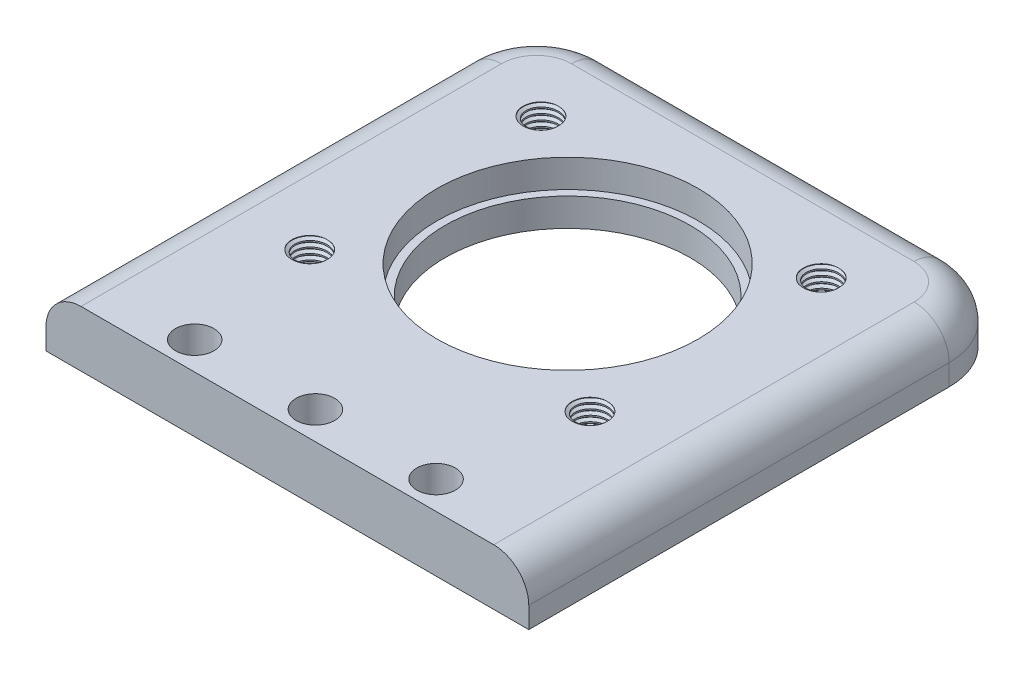
SolidWorks part; units mm, degrees
ref_plane "Front Plane" through (0, 0, 0) normal (0, 0, 1) x (1, 0, 0)
ref_plane "Top Plane" through (0, 0, 0) normal (0, 1, 0) x (1, 0, 0)
ref_plane "Right Plane" through (0, 0, 0) normal (1, 0, 0) x (0, 0, -1)
sketch "Sketch1" plane through (0, 0, 0) normal (0, 1, 0) x (1, 0, 0)
  line L1 (0, 0) -> (68.9, 0)
  line L2 (0, 0) -> (0, 70)
  line L3 (0, 70) -> (68.9, 70)
  line L4 (68.9, 0) -> (68.9, 70)
  circle A0 centre (34.45, 40) radius 18.63
  circle A1 centre (34.45, 4) radius 2.75
  circle A2 centre (17.225, 4) radius 2.75
  circle A3 centre (51.675, 4) radius 2.75
  dimension "D3" = 34.45
  dimension "D5" = 34.45
  dimension "D8" = 4
  dimension "D1" = 68.9
  dimension "D2" = 70
  dimension "D4" = 30
  dimension "D6" = 17.225
  dimension "D7" = 17.225
extrude "Boss-Extrude1" add sketch "Sketch1" along normal blind 8
fillet "Fillet1" radius 10 2 edges at (68.9, 4, -70) (0, 4, -70)
fillet "Fillet2" radius 5 5 edges at (65.9711, 8, -67.0711) (34.45, 8, -70) (2.9289, 8, -67.0711) (68.9, 8, -30) (0, 8, -30)
sketch "Sketch2" plane through (0, 0, 0) normal (0, -1, 0) x (1, 0, 0)
  circle A0 centre (34.45, -40) radius 18.63
  circle A1 centre (34.45, -40) radius 17.5
extrude "Boss-Extrude2" add sketch "Sketch2" against normal blind 4
sketch "Sketch5" plane through (0, 8, 0) normal (0, 1, 0) x (1, 0, 0)
  line L1 (54.45, 23.5) -> (14.45, 23.5)
  line L2 (54.45, 23.5) -> (54.45, 56.5)
  line L3 (54.45, 56.5) -> (14.45, 56.5)
  line L4 (14.45, 23.5) -> (14.45, 56.5)
  line L5 (54.45, 23.5) -> (14.45, 56.5) construction
  line L6 (54.45, 56.5) -> (14.45, 23.5) construction
  circle A0 centre (14.45, 56.5) radius 2.3
  circle A1 centre (54.45, 56.5) radius 2.3
  circle A2 centre (54.45, 23.5) radius 2.3
  circle A3 centre (14.45, 23.5) radius 2.3
  point P0 (34.45, 40)
  dimension "D1" = 40
  dimension "D2" = 33
extrude "Cut-Extrude1" cut sketch "Sketch5" against normal blind 6 contours L3 A0 L4 | L4 A0 L3 | L2 A1 L3 | L1 A2 L2 | L4 A3 L1 | L1 A3 L4 | L2 A2 L1 region at (14.1246, 8, -23.1746) region at (15.4262, 8, -24.4762) region at (53.4738, 8, -24.4762) region at (54.7754, 8, -23.1746) region at (14.1246, 8, -56.8254) region at (15.4262, 8, -55.5238) region at (54.7754, 8, -56.8254)
thread "Thread1" pitch 0.8 method cut profile "Thread Profile1" start angle 0, offset 1, length 0, pitch 0.8, diameter 4.6
ref_plane "Plane1" through (12.15, 9, -56.5) normal (0, 0, 1) x (-1, 0, 0)
sketch "Thread Profile1" plane through (12.15, 9, -56.5) normal (0, 0, 1) x (-1, 0, 0)
  line L0 (0, 0) -> (0, 0.8) construction
  line L1 (0, 0) -> (0.433, 0.25)
  line L2 (0.433, 0.25) -> (0.433, 0.35)
  line L3 (0.433, 0.35) -> (0, 0.6)
  line L4 (0.433, 0.3) -> (0, 0.3) construction
  line L11 (0, 0) -> (0, 0.6)
  point P2 (0, 0)
  dimension "Pitch" = 0.8
  dimension "Profile_Angle" = 60
  dimension "Profile_Land" = 0.1
  dimension "Profile_Height" = 0.433
thread "Thread2" pitch 0.8 method cut profile "Thread Profile2" start angle 0, offset 1, length 0, pitch 0.8, diameter 4.6
ref_plane "Plane2" through (52.15, 9, -23.5) normal (0, 0, 1) x (-1, 0, 0)
sketch "Thread Profile2" plane through (52.15, 9, -23.5) normal (0, 0, 1) x (-1, 0, 0)
  line L0 (0, 0) -> (0, 0.8) construction
  line L1 (0, 0) -> (0.433, 0.25)
  line L2 (0.433, 0.25) -> (0.433, 0.35)
  line L3 (0.433, 0.35) -> (0, 0.6)
  line L4 (0.433, 0.3) -> (0, 0.3) construction
  line L11 (0, 0) -> (0, 0.6)
  point P2 (0, 0)
  dimension "Pitch" = 0.8
  dimension "Profile_Angle" = 60
  dimension "Profile_Land" = 0.1
  dimension "Profile_Height" = 0.433
thread "Thread3" pitch 0.8 method cut profile "Thread Profile3" start angle 0, offset 1, length 0, pitch 0.8, diameter 4.6
ref_plane "Plane3" through (12.15, 9, -23.5) normal (0, 0, 1) x (-1, 0, 0)
sketch "Thread Profile3" plane through (12.15, 9, -23.5) normal (0, 0, 1) x (-1, 0, 0)
  line L0 (0, 0) -> (0, 0.8) construction
  line L1 (0, 0) -> (0.433, 0.25)
  line L2 (0.433, 0.25) -> (0.433, 0.35)
  line L3 (0.433, 0.35) -> (0, 0.6)
  line L4 (0.433, 0.3) -> (0, 0.3) construction
  line L11 (0, 0) -> (0, 0.6)
  point P2 (0, 0)
  dimension "Pitch" = 0.8
  dimension "Profile_Angle" = 60
  dimension "Profile_Land" = 0.1
  dimension "Profile_Height" = 0.433
extrude "Cut-Extrude2" cut sketch "Sketch5<3>" against normal blind 6 contours L3 A1 L2 region at (53.4738, 8, -55.5238)
sketch "Sketch5<3>" plane through (0, 8, 0) normal (0, 1, 0) x (1, 0, 0) same geometry as "Sketch5"
thread "Thread4" pitch 0.8 method cut profile "Thread Profile4" start angle 0, offset 1, length 0, pitch 0.8, diameter 4.6
ref_plane "Plane4" through (52.15, 9, -56.5) normal (0, 0, 1) x (-1, 0, 0)
sketch "Thread Profile4" plane through (52.15, 9, -56.5) normal (0, 0, 1) x (-1, 0, 0)
  line L0 (0, 0) -> (0, 0.8) construction
  line L1 (0, 0) -> (0.433, 0.25)
  line L2 (0.433, 0.25) -> (0.433, 0.35)
  line L3 (0.433, 0.35) -> (0, 0.6)
  line L4 (0.433, 0.3) -> (0, 0.3) construction
  line L11 (0, 0) -> (0, 0.6)
  point P2 (0, 0)
  dimension "Pitch" = 0.8
  dimension "Profile_Angle" = 60
  dimension "Profile_Land" = 0.1
  dimension "Profile_Height" = 0.433
sketch "Sketch14" plane through (0, 8, 0) normal (0, 1, 0) x (1, 0, 0)
  circle A0 centre (34.45, 40) radius 23.3345
